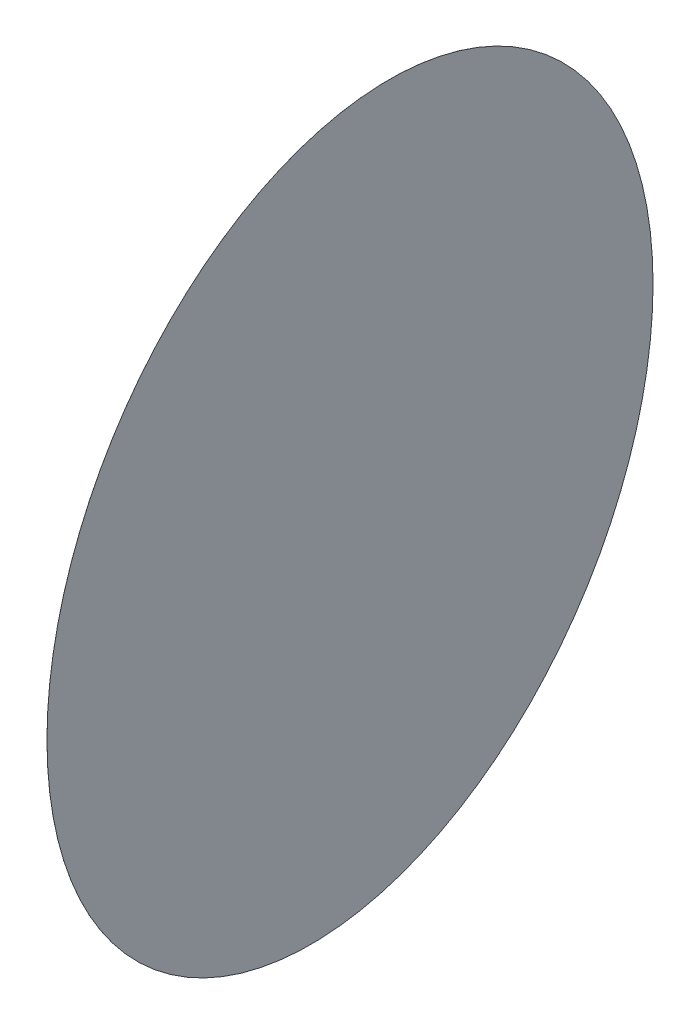
SolidWorks part; units mm, degrees
ref_plane "Front Plane" through (0, 0, 0) normal (0, 0, 1) x (1, 0, 0)
ref_plane "Top Plane" through (0, 0, 0) normal (0, 1, 0) x (1, 0, 0)
ref_plane "Right Plane" through (0, 0, 0) normal (1, 0, 0) x (0, 0, -1)
sketch3d "3DSketch1"
  line L2 (-24.3505, 0, -31.7341) -> (0, 0, 0) construction
  line L3 (0, 0, 0) -> (-15.3073, 0, -36.9552) construction
  line L4 (0, 0, 0) -> (39.6578, 0, -5.221) construction
  line L5 (39.6578, 0, 5.221) -> (0, 0, 0) construction
  line L6 (-15.3073, 0, 36.9552) -> (-2.1567, 4.7319, 42.4023)
  line L7 (-15.3073, 0, 36.9552) -> (0, 0, 0) construction
  line L8 (0, 0, 0) -> (-24.3505, 0, 31.7341) construction
  line L9 (42.285, 0, 78.0778) -> (50.1338, 0, 90.8604)
  line L10 (-24.3505, 0, 31.7341) -> (-35.6431, 4.7319, 23.069)
  line L11 (0, 0, 0) -> (42.8187, 0, 0) construction
  line L12 (-24.3505, 0, -31.7341) -> (-35.6431, 4.7319, -23.069)
  line L13 (-15.3073, 0, -36.9552) -> (-2.1567, 4.7319, -42.4023)
  line L14 (39.6578, 0, -5.221) -> (37.7999, 4.7319, -19.3334)
  line L15 (39.6578, 0, 5.221) -> (37.7999, 4.7319, 19.3334)
  line L16 (30, 40, 0) -> (0, 40, 0) construction
  line L17 (19.2836, 40, 22.9813) -> (0, 40, 0) construction
  line L18 (0, 40, 0) -> (19.2836, 40, -22.9813) construction
  line L19 (10.2606, 40, -28.1908) -> (0, 40, 0) construction
  line L20 (0, 40, 0) -> (-29.5442, 40, -5.2094) construction
  line L21 (-29.5442, 40, 5.2094) -> (0, 40, 0) construction
  line L22 (0, 40, 0) -> (10.2606, 40, 28.1908) construction
  line L23 (77.8401, 0, 43.6828) -> (101.0559, 0, 76.2562)
  line L24 (19.2836, 40, 22.9813) -> (37.7999, 4.7319, 19.3334)
  line L25 (19.2836, 40, -22.9813) -> (37.7999, 4.7319, -19.3334)
  line L26 (10.2606, 40, 28.1908) -> (-2.1567, 4.7319, 42.4023)
  line L27 (-29.5442, 40, 5.2094) -> (-35.6431, 4.7319, 23.069)
  line L28 (-35.6431, 4.7319, -23.069) -> (-29.5442, 40, -5.2094)
  line L29 (-2.1567, 4.7319, -42.4023) -> (10.2606, 40, -28.1908)
  line L30 (39.6578, 0, 5.221) -> (39.6578, 6.5786, 5.221)
  circle A1 centre (0, 0, 0) radius 40
  circle A2 centre (0, 40, 0) radius 30
  point P3 (0, 40, 0)
  point P23 (0, 70, 0)
  point P30 (39.6578, 6.5786, 5.221)
  dimension "D2" = 15
  dimension "D1" = 80
  dimension "D9" = 60
  dimension "D3" = 15
  dimension "D4" = 15
  dimension "D5" = 105
  dimension "D6" = 105
  dimension "D7" = 15
  dimension "D8" = 7.5
  dimension "D10" = 100
  dimension "D11" = 50
  dimension "D12" = 100
  dimension "D13" = 100
  dimension "D14" = 20
  dimension "D15" = 20
  dimension "D16" = 40
  dimension "D17" = 40
  dimension "D18" = 71.612
sketch3d "3D草图1"
  line L4 (0, 0, 0) -> (58.3341, 0, 0) construction
  line L5 (0, 22.6988, 0) -> (0, -14.0197, 0) construction
  line L6 (0, 0, 0) -> (0, 0, -50000) construction
sketch3d "3D草图2"
  line L0 (19.2836, 40, -22.9813) -> (37.7999, 4.7319, -19.3334) construction
  line L1 (0, 40, 0) -> (19.2836, 40, -22.9813) construction
  line L2 (0, 0, 0) -> (39.6578, 0, -5.221) construction
  line L3 (39.6578, 0, -5.221) -> (37.7999, 4.7319, -19.3334) construction
  line L4 (19.2836, 40, -22.9813) -> (37.7999, 4.7319, -19.3334)
  line L5 (0, 40, 0) -> (19.2836, 40, -22.9813)
  line L6 (0, 0, 0) -> (39.6578, 0, -5.221)
  line L7 (39.6578, 0, -5.221) -> (37.7999, 4.7319, -19.3334)
  line L8 (19.2836, 40, -22.9813) -> (39.6578, 0, -5.221) construction
sketch3d "3D草图3"
  line L0 (0, 0, 0) -> (39.6578, 0, -5.221) construction
sketch "草图1" plane through (39.6578, 0, -5.221) normal (-0.9914, 0, 0.1305) x (0.1305, 0, 0.9914)
  circle A0 centre (0, 0) radius 15
extrude "凸台-拉伸1" add sketch "草图1" against normal blind 0.001
sketch "草图2" plane through (39.6578, 0, -5.221) normal (-0.9914, 0, 0.1305) x (0.1305, 0, 0.9914)
  line L1 (-20.2677, 40) -> (-14.2341, 4.7319) construction
  line L2 (-20.2677, 40) -> (0, 0) construction
  line L3 (-20.2677, 40) -> (-14.2341, 4.7319)
  line L4 (0, 0) -> (-14.2341, 4.7319) construction
  dimension "D1" = 44.741
sketch3d "3D草图4"
  line L0 (19.2836, 40, -22.9813) -> (37.0123, 40, -25.3154) construction
  line L1 (0, 0, 0) -> (39.6578, 0, -5.221) construction
equation "\"servo_angle\"= 15"
equation "\"D2@3DSketch1\"=\"servo_angle\""
equation "\"D3@3DSketch1\"=\"servo_angle\""
equation "\"D4@3DSketch1\"=\"servo_angle\""
equation "\"D5@3DSketch1\"=(360-\"servo_angle\"*3)/3"
equation "\"D6@3DSketch1\"=(360-\"servo_angle\"*3)/3"
equation "\"servo_arm_length\"=15"
equation "\"D7@3DSketch1\"=\"servo_arm_length\""
equation "\"D8@3DSketch1\"=\"servo_angle\"/2"
equation "\"top_diameter\"=60"
equation "\"D9@3DSketch1\"=\"top_diameter\""
equation "\"top_angle\"= 100"
equation "\"D10@3DSketch1\"=\"top_angle\""
equation "\"D11@3DSketch1\"=\"top_angle\"/2"
equation "\"D12@3DSketch1\"=\"top_angle\""
equation "\"D13@3DSketch1\"=\"top_angle\""
equation "\"D14@3DSketch1\"=(360-\"top_angle\"*3)/3"
equation "\"D15@3DSketch1\"=(360-\"top_angle\"*3)/3"
equation "\"leg_length\"=40"
equation "\"D16@3DSketch1\"=\"leg_length\""
equation "\"Base_diameter\"= 80"
equation "\"D1@3DSketch1\"=\"Base_diameter\""
